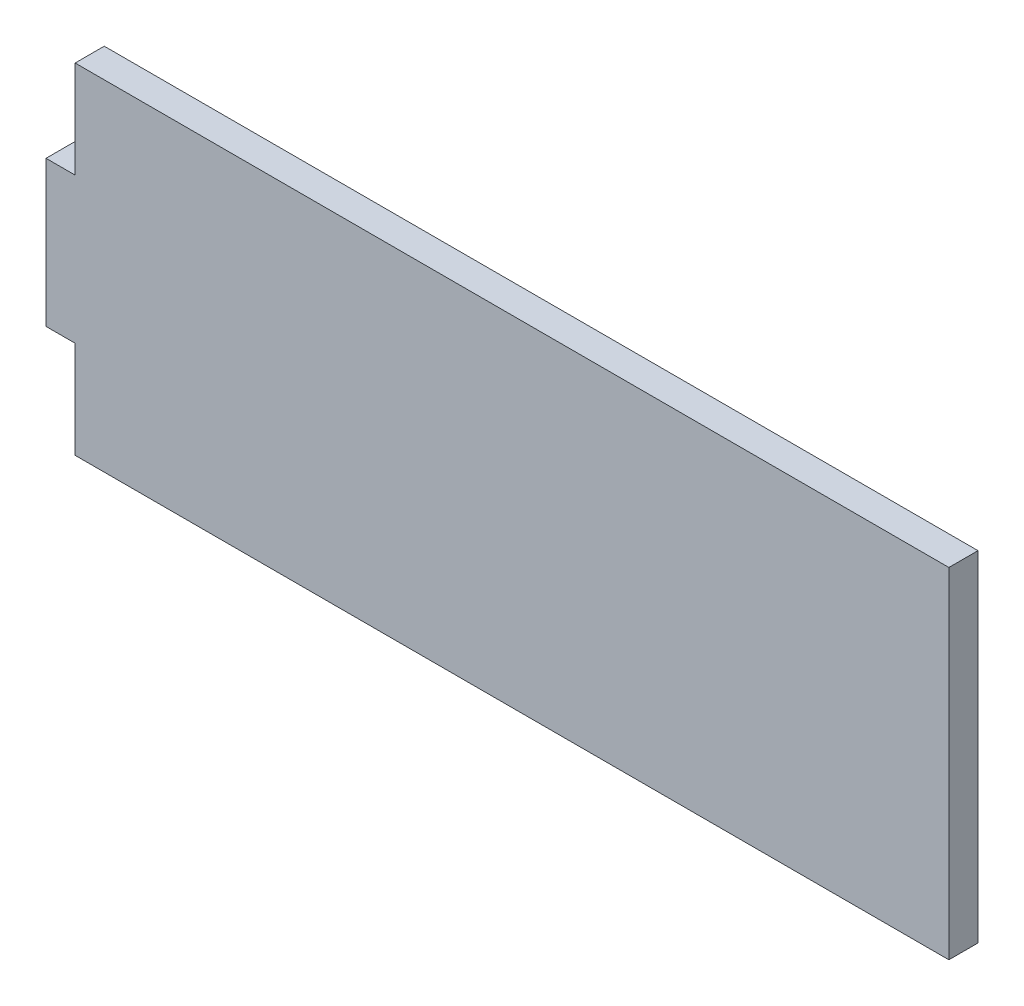
SolidWorks part; units mm, degrees
ref_plane "Front Plane" through (0, 0, 0) normal (0, 0, 1) x (1, 0, 0)
ref_plane "Top Plane" through (0, 0, 0) normal (0, 1, 0) x (1, 0, 0)
ref_plane "Right Plane" through (0, 0, 0) normal (1, 0, 0) x (0, 0, -1)
sketch "Sketch1" plane through (0, 0, 0) normal (0, 0, 1) x (1, 0, 0)
  line L1 (-45, -17.5) -> (45, -17.5)
  line L2 (-45, -17.5) -> (-45, 17.5)
  line L3 (-45, 17.5) -> (45, 17.5)
  line L4 (45, -17.5) -> (45, 17.5)
  line L5 (-45, -17.5) -> (45, 17.5) construction
  line L6 (-45, 17.5) -> (45, -17.5) construction
  line L7 (-45, 7.5) -> (-48, 7.5)
  line L8 (-45, 7.5) -> (-45, -7.5)
  line L9 (-45, -7.5) -> (-48, -7.5)
  line L10 (-48, 7.5) -> (-48, -7.5)
  point P0 (0, 0)
  point P10 (-48, 0)
  point P11 (-46.5, -7.5)
  dimension "D1" = 90
  dimension "D2" = 10
  dimension "D3" = 15
  dimension "D4" = 3
extrude "Boss-Extrude1" add sketch "Sketch1" along normal mid plane 3 contours L1 L4 L3 L2 | L7 L10 L9 L2 region at (0, 0, 0) region at (-46.5, 0, 0)
